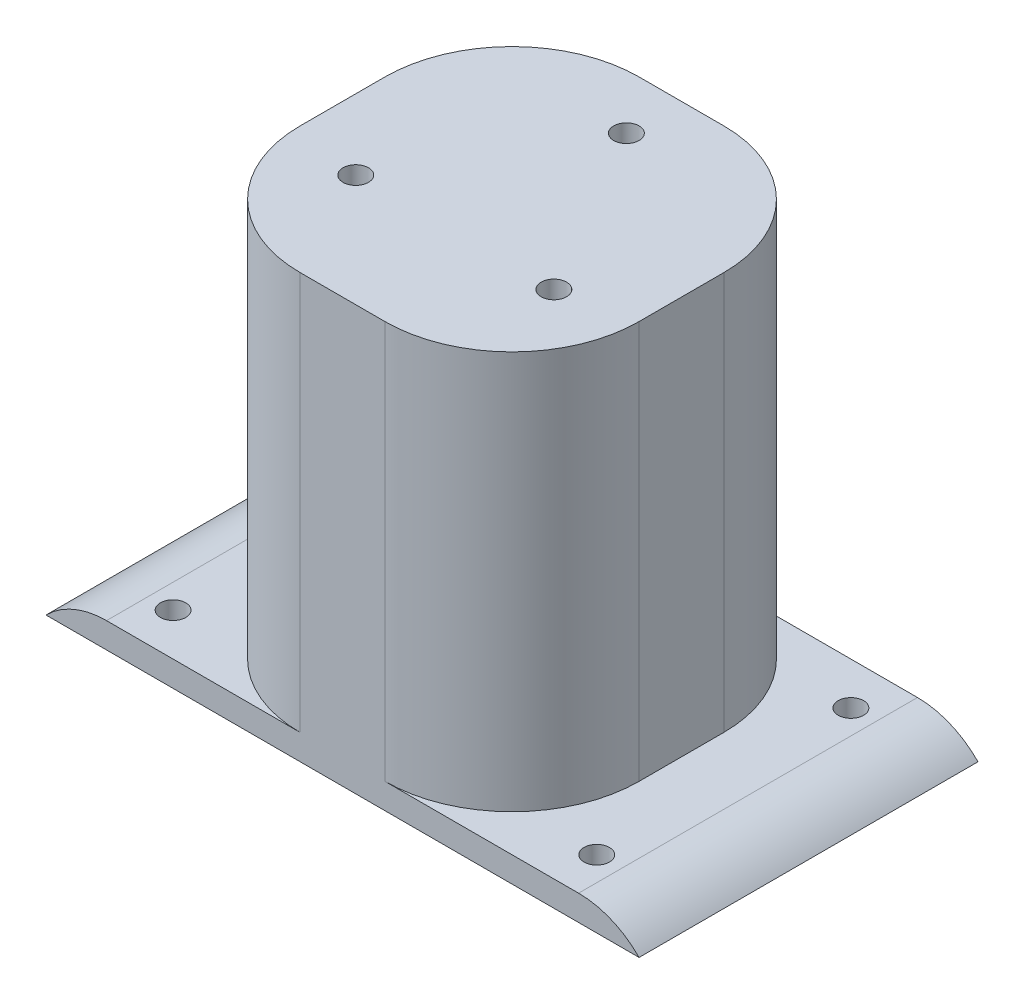
SolidWorks part; units mm, degrees
ref_plane "Front Plane" through (0, 0, 0) normal (0, 0, 1) x (1, 0, 0)
ref_plane "Top Plane" through (0, 0, 0) normal (0, 1, 0) x (1, 0, 0)
ref_plane "Right Plane" through (0, 0, 0) normal (1, 0, 0) x (0, 0, -1)
sketch "Sketch1" plane through (0, 0, 0) normal (0, 1, 0) x (1, 0, 0)
  line L0 (0, 0) -> (0, 33.0068) construction
  line L1 (35, -20) -> (-35, -20)
  line L2 (35, -20) -> (35, 20)
  line L3 (35, 20) -> (-35, 20)
  line L4 (-35, -20) -> (-35, 20)
  line L5 (35, -20) -> (-35, 20) construction
  line L6 (35, 20) -> (-35, -20) construction
  line L7 (20, -20) -> (-20, -20)
  line L8 (20, -20) -> (20, 20)
  line L9 (20, 20) -> (-20, 20)
  line L10 (-20, -20) -> (-20, 20)
  line L11 (20, -20) -> (-20, 20) construction
  line L12 (20, 20) -> (-20, -20) construction
  line L13 (0, 0) -> (35.9575, 0) construction
  circle A0 centre (0, 0) radius 13.5 construction
  circle A1 centre (0, 13.5) radius 1.5
  circle A2 centre (11.6913, -6.75) radius 1.5
  circle A3 centre (-11.6913, -6.75) radius 1.5
  circle A4 centre (-25, 15) radius 1.5
  circle A5 centre (-25, -15) radius 1.5
  circle A6 centre (25, -15) radius 1.5
  circle A7 centre (25, 15) radius 1.5
  point P0 (0, 0)
  point P16 (0, 0)
  dimension "D3" = 27
  dimension "D4" = 3
  dimension "D9" = 3
  dimension "D1" = 70
  dimension "D2" = 40
  dimension "D6" = 11.6913
  dimension "D7" = 6.75
  dimension "D8" = 40
  dimension "D10" = 25
  dimension "D11" = 15
  dimension "D5" = 3
extrude "Boss-Extrude1" add sketch "Sketch1" along normal blind 50 contours L10 L1 L8 L3 A3 A2 A1 region at (0, 0, 0)
extrude "Boss-Extrude2" add sketch "Sketch1<3>" along normal blind 3 contours L1 L10 L3 L4 A4 A5 | L8 L1 L2 L3 A6 A7 region at (27.5603, 0, 0) region at (-27.5603, 0, 0)
sketch "Sketch1<3>" plane through (0, 0, 0) normal (0, 1, 0) x (1, 0, 0) same geometry as "Sketch1"
fillet "Fillet1" radius 10 2 edges at (35, 3, 0) (-35, 3, 0)
fillet "Fillet2" radius 15 4 edges at (-20, 26.5, 20) (-20, 26.5, -20) (20, 26.5, -20) (20, 26.5, 20)
